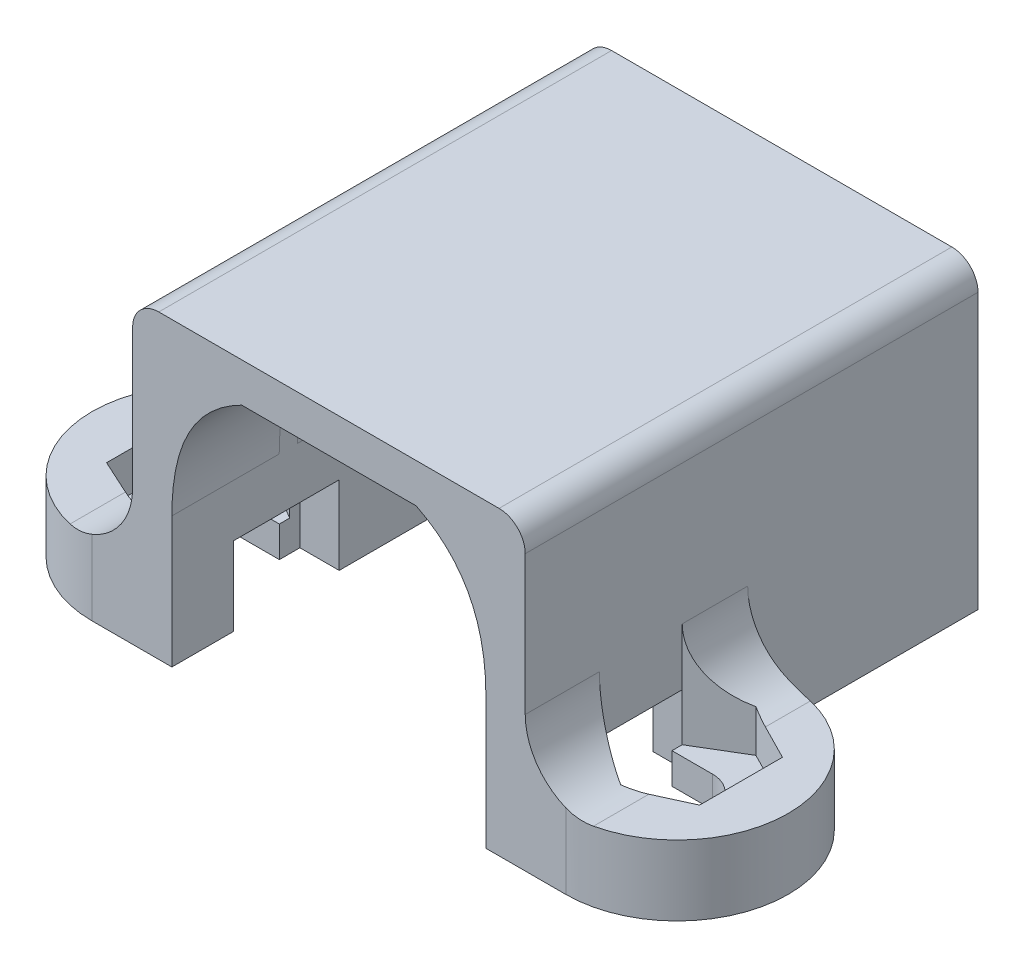
SolidWorks part; units mm, degrees
ref_plane "Front Plane" through (0, 0, 0) normal (0, 0, 1) x (1, 0, 0)
ref_plane "Top Plane" through (0, 0, 0) normal (0, 1, 0) x (1, 0, 0)
ref_plane "Right Plane" through (0, 0, 0) normal (1, 0, 0) x (0, 0, -1)
sketch "Sketch2" plane through (0, 0, 0) normal (0, 0, 1) x (1, 0, 0)
  line L1 (-13.3, 5.75) -> (13.3, 5.75)
  line L2 (-13.3, 5.75) -> (-13.3, -5.75)
  line L3 (-13.3, -5.75) -> (13.3, -5.75)
  line L4 (13.3, 5.75) -> (13.3, -5.75)
  line L5 (-13.3, 5.75) -> (13.3, -5.75) construction
  line L6 (-13.3, -5.75) -> (13.3, 5.75) construction
  point P0 (0, 0)
  dimension "D1" = 11.5
  dimension "D2" = 26.6
extrude "Boss-Extrude1" add sketch "Sketch2" along normal blind 8.65 and the other way blind 8.65
sketch "Sketch3" plane through (0, 0, 8.65) normal (0, 0, 1) x (1, 0, 0)
  line L0 (-7.5, 5.75) -> (-7.5, -0.5708)
  line L1 (13.3, 5.75) -> (-13.3, 5.75) construction
  line L2 (-10, -3.0708) -> (-13.3, -3.0708)
  line L3 (-13.3, 5.75) -> (-13.3, -5.75) construction
  line L4 (-13.3, -3.0708) -> (-13.3, 5.75)
  line L5 (-13.3, 5.75) -> (-7.5, 5.75)
  line L6 (7.5, 5.75) -> (7.5, -0.5708)
  line L7 (10, -3.0708) -> (13.3, -3.0708)
  line L8 (13.3, -5.75) -> (13.3, 5.75) construction
  line L9 (13.3, -3.0708) -> (13.3, 5.75)
  line L10 (13.3, 5.75) -> (7.5, 5.75)
  arc A0 (7.5, -0.5708) -> (10, -3.0708) centre (10, -0.5708) ccw
  arc A1 (-7.5, -0.5708) -> (-10, -3.0708) centre (-10, -0.5708) cw
  dimension "D1" = 2.5
  dimension "D2" = 7.5
  dimension "D3" = 7.5
extrude "Cut-Extrude1" cut sketch "Sketch3" against normal through all
sketch "Sketch4" plane through (0, -5.75, 0) normal (0, -1, 0) x (1, 0, 0)
  line L1 (-13.3, -8.65) -> (-7.5, -8.65)
  line L2 (-13.3, -8.65) -> (-13.3, 0.15)
  line L3 (-13.3, 0.15) -> (-7.5, 0.15)
  line L4 (-7.5, -8.65) -> (-7.5, 0.15)
  line L5 (13.3, -8.65) -> (7.5, -8.65)
  line L6 (13.3, -8.65) -> (13.3, 0.15)
  line L7 (13.3, 0.15) -> (7.5, 0.15)
  line L8 (7.5, -8.65) -> (7.5, 0.15)
  dimension "D1" = 8.8
  dimension "D2" = 5.8
  dimension "D3" = 8.8
  dimension "D4" = 5.8
extrude "Cut-Extrude2" cut sketch "Sketch4" against normal through all
sketch "Sketch5" plane through (0, -5.75, 0) normal (0, -1, 0) x (1, 0, 0)
  line L0 (-13.3, 0.15) -> (-13.3, 8.65) construction
  line L1 (-9.05, 3.0436) -> (-7.5, 3.0436)
  line L2 (-7.5, 3.0436) -> (-7.5, 5.3436)
  line L3 (-7.5, 5.3436) -> (-9.05, 5.3436)
  line L4 (-7.5, 6.2886) -> (-7.5, 2.2586)
  line L5 (-7.5, 2.2586) -> (-6, 2.2586)
  line L6 (-6, 2.2586) -> (-6, 6.2886)
  line L7 (-6, 6.2886) -> (-7.5, 6.2886)
  arc A0 (-9.05, 3.0436) -> (-9.05, 5.3436) centre (-9.05, 4.1936) cw
  dimension "D1" = 4.25
  dimension "D2" = 4.03
extrude "Cut-Extrude3" cut sketch "Sketch5" against normal blind 3 contours L7 L4 L5 L6
extrude "Cut-Extrude4" cut sketch "Sketch5<3>" against normal blind 1.4 contours A0 L1 L2 L3 region at (-8.74, -5.75, 4.1936)
sketch "Sketch5<3>" plane through (0, -5.75, 0) normal (0, -1, 0) x (1, 0, 0) same geometry as "Sketch5"
sketch "Sketch8" plane through (0, -5.75, 0) normal (0, -1, 0) x (1, 0, 0)
  line L1 (-11.3295, 5.8161) -> (-11.3295, 2.6511)
  line L2 (-11.3295, 2.6511) -> (-9.2597, 1.5963)
  line L3 (-9.2597, 1.5963) -> (-7.5, 2.6511)
  line L4 (-7.5, 2.6511) -> (-7.5, 5.8161)
  line L5 (-7.5, 5.8161) -> (-9.2597, 6.7639)
  line L6 (-9.2597, 6.7639) -> (-11.3295, 5.8161)
  line L7 (-7.5, 2.2586) -> (-6, 2.2586) construction
  line L8 (-7.5, 6.2886) -> (-7.5, 2.2586) construction
  point P0 (-9.2597, 6.7639)
  point P1 (-7.5, 3.2989)
extrude "Cut-Extrude5" cut sketch "Sketch8" along normal blind 4 from vertex starting at point (-7.5, -0.5708, 0.15)
fillet "Fillet3" 2 edges at (-13.3, -4.4104, 0.15) (-13.3, -4.4104, 8.65) type full round first side face at (-10.2164, -3.746, 0.15) second side face at (0, -1.446, 8.65) middle face at (-13.3, -4.4104, 4.4)
mirror "Mirror4" about plane through (0, 0, 0) normal (1, 0, 0) of "Cut-Extrude5", "Cut-Extrude4", "Cut-Extrude3"
fillet "Fillet4" 2 edges at (13.3, -4.4104, 0.15) (13.3, -4.4104, 8.65) type full round first side face at (10.2164, -3.746, 0.15) second side face at (2.0371, -1.2133, 8.65) middle face at (13.3, -4.4104, 4.4)
sketch "Sketch10" plane through (0, 0, 8.65) normal (0, 0, 1) x (1, 0, 0)
  line L0 (0, -6.325) -> (0, 6.325) construction
  line L1 (-6, -5.75) -> (6, -5.75)
  line L5 (6, -0.75) -> (6, 1.3423) construction
  line L6 (-6, -5.75) -> (-6, -0.75)
  line L7 (6, -5.75) -> (6, -0.75)
  line L9 (-3.3315, 4.25) -> (3.2972, 4.25)
  line L11 (-6, -0.75) -> (-6, 1.3423) construction
  line L12 (-6, 1.3423) -> (-5.3977, 3.2197) construction
  line L13 (-5.3977, 3.2197) -> (-3.3315, 4.25) construction
  line L14 (6, 1.3423) -> (5.3977, 3.2197) construction
  line L15 (5.3977, 3.2197) -> (3.3315, 4.25) construction
  line L16 (3.2972, 4.25) -> (3.3315, 4.25)
  spline S0 degree 3 poles (-6, -0.75) (-6, 1.3423) (-5.3977, 3.2197) (-3.3315, 4.25) knots 0 0 0 0 1 1 1 1
  spline S1 degree 3 poles (6, -0.75) (6, 1.3423) (5.3977, 3.2197) (3.3315, 4.25) knots 0 0 0 0 1 1 1 1
extrude "Cut-Extrude6" cut sketch "Sketch10" against normal through all
fillet "Fillet5" radius 1 2 edges at (7.5, 5.75, 0) (-7.5, 5.75, 0)
sketch "Sketch12" plane through (0, -5.75, 0) normal (0, -1, 0) x (1, 0, 0)
  line L0 (6, -8.65) -> (6, 8.65) construction
  line L1 (-6, -8.65) -> (6, -8.65)
  line L2 (-6, -8.65) -> (-6, -7.25)
  line L3 (-6, -7.25) -> (6, -7.25)
  line L4 (6, -8.65) -> (6, -7.25)
  line L6 (-6, -8.65) -> (-6, 8.65) construction
  line L7 (-6, 0.35) -> (6, 0.35)
  line L8 (-6, 0.35) -> (-6, 1.05)
  line L9 (-6, 1.05) -> (6, 1.05)
  line L10 (6, 0.35) -> (6, 1.05)
  line L11 (-6, -8.65) -> (-6, 2.2586) construction
  line L12 (-6, 3.85) -> (6, 3.85)
  line L13 (-6, 3.85) -> (-6, 4.55)
  line L14 (-6, 4.55) -> (6, 4.55)
  line L15 (6, 3.85) -> (6, 4.55)
  dimension "D1" = 1.4
  dimension "D2" = 0.7
  dimension "D3" = 7.6
  dimension "D4" = 0.7
  dimension "D5" = 2.8
extrude "Cut-Extrude7" cut sketch "Sketch12" against normal up to surface (10 mm away) up to face at (0, 4.25, 0)
